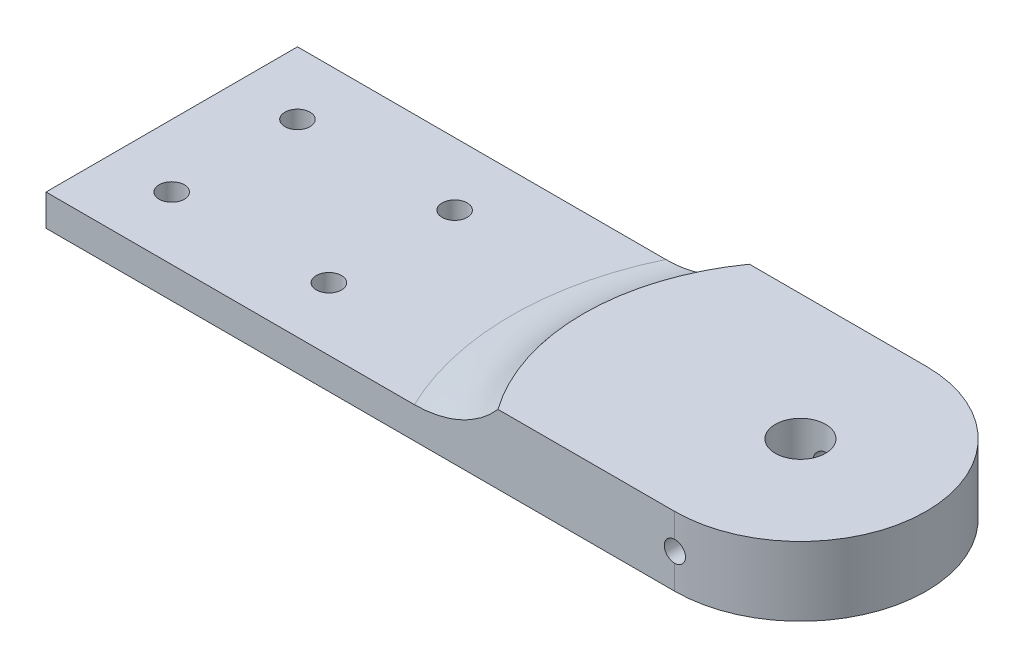
SolidWorks part; units mm, degrees
material "1060 Alloy"
ref_plane "Front Plane" through (0, 0, 0) normal (0, 0, 1) x (1, 0, 0)
ref_plane "Top Plane" through (0, 0, 0) normal (0, 1, 0) x (1, 0, 0)
ref_plane "Right Plane" through (0, 0, 0) normal (1, 0, 0) x (0, 0, -1)
sketch "Sketch1" plane through (0, 0, 0) normal (0, 1, 0) x (1, 0, 0)
  line L0 (-100, 20) -> (20, 20)
  line L1 (20, 20) -> (20, -5)
  line L2 (20, -5) -> (-100, -5) construction
  line L3 (-100, -5) -> (-100, 20)
  line L4 (20, -5) -> (20, -20)
  line L5 (20, -20) -> (-100, -20)
  line L6 (-100, -20) -> (-100, -5)
  line L7 (20, -10) -> (-90, -10) construction
  line L8 (-90, -10) -> (-90, -5) construction
  line L9 (-90, -5) -> (-90, 10) construction
  line L10 (-90, 10) -> (20, 10) construction
  circle A0 centre (0, 0) radius 4
  circle A1 centre (-90, 10) radius 2
  circle A2 centre (-65, 10) radius 2
  circle A3 centre (-65, -10) radius 2
  circle A4 centre (-90, -10) radius 2
  arc A5 (0, -20) -> (0, 20) centre (0, 0) ccw
  dimension "D1" = 8
  dimension "D7" = 4
  dimension "D2" = 20
  dimension "D3" = 25
  dimension "D4" = 20
  dimension "D5" = 15
  dimension "D6" = 120
  dimension "D9" = 25
  dimension "D8" = 10
extrude "Boss-Extrude1" add sketch "Sketch1" along normal blind 11 contours L5 A5 L0 L3 L6 A4 A3 A2 A1 A0 region at (-42.1334, 0, 0)
sketch "Sketch4" plane through (0, 11, 0) normal (0, 1, 0) x (1, 0, 0)
  line L0 (-28.1114, 20) -> (-100, 20)
  line L1 (-100, 20) -> (-100, -20)
  line L2 (-100, -20) -> (-28.1114, -20)
  arc A1 (-28.1114, 20) -> (-28.1114, -20) centre (0, 0) ccw
  point P1 (0, 0)
  point P2 (-17.7794, -20)
  point P3 (-22.3853, 20)
  point P5 (-19.8104, 20)
  point P9 (-19.8104, -20)
  dimension "D1" = 69
extrude "Cut-Extrude1" cut sketch "Sketch4" against normal offset from surface (6 mm away) 5 up to face at (-90, 0, 12)
fillet "Fillet2" radius 14 1 edges at (-34.5, 5, 0)
hole_wizard "M4 Tapped Hole1" positions "Sketch2" profile "Sketch3" tap size "M4" standard "ISO" end condition through all
sketch "Sketch2" plane through (0, 0, -20) normal (0, 0, -1) x (-1, 0, 0)
  line L0 (0, 6.05) -> (0, -6.05) construction
  line L1 (0, 11) -> (0, 0) construction
  point P0 (0, 5.5)
  point P11 (0, 5.5)
cosmetic thread "Hole Thread1" parameters "D2"=4
sketch "Sketch3" plane through (0, 5.5, -20) normal (1, 0, 0) x (0, 1, 0)
  line L0 (0, 0) -> (0, 40)
  line L1 (0, 40) -> (1.65, 40)
  line L2 (1.65, 40) -> (1.65, 0)
  line L5 (1.65, 0) -> (0, 0)
  line L11 (0, -6.35) -> (0, 107.95) construction
  dimension "Thru Tap Drill Dia." = 3.3
  dimension "Thru Tap Drill Depth" = 40
